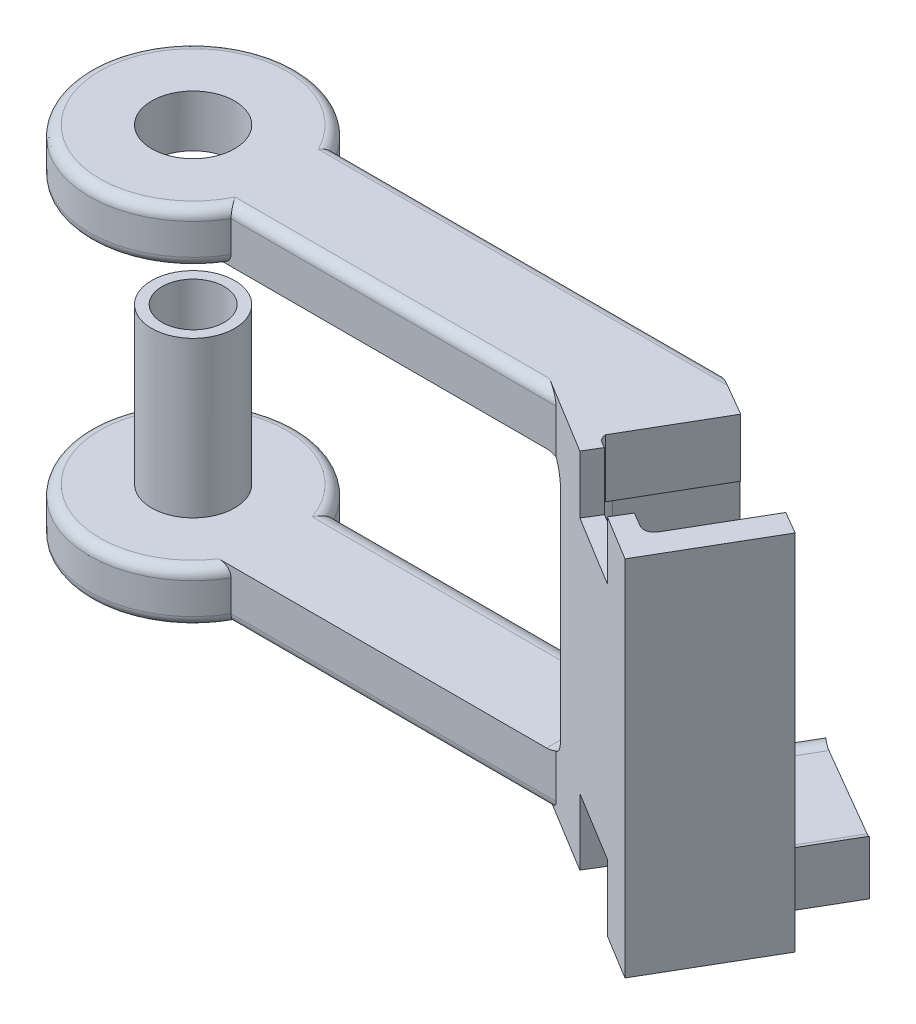
SolidWorks part; units mm, degrees
ref_plane "Front Plane" through (0, 0, 0) normal (0, 0, 1) x (1, 0, 0)
ref_plane "Top Plane" through (0, 0, 0) normal (0, 1, 0) x (1, 0, 0)
ref_plane "Right Plane" through (0, 0, 0) normal (1, 0, 0) x (0, 0, -1)
sketch "Sketch2" plane through (0, 0, 0) normal (0, 1, 0) x (1, 0, 0)
  line L0 (-20, 0) -> (20, 0) construction
  line L1 (-20, 5) -> (20, 5)
  line L2 (-20, -5) -> (20, -5)
  line L8 (25.8152, 5) -> (43.1044, -5.054)
  line L9 (20, -5) -> (37.068, -15.4252)
  line L10 (43.1044, -5.054) -> (37.068, -15.4252)
  line L11 (20, 5) -> (25.8152, 5)
  arc A0 (-20, 5) -> (-20, -5) centre (-20, 0) ccw
  circle A2 centre (-20, 0) radius 3
  point P2 (0, 0)
  dimension "D1" = 40
  dimension "D3" = 6
  dimension "D2" = 10
  dimension "D4" = 20
  dimension "D5" = 12
extrude "Boss-Extrude2" add sketch "Sketch2" along normal blind 35
sketch "Sketch3" plane through (0, 0, -5) normal (0, 0, -1) x (-1, 0, 0)
  line L6 (27.167, 30) -> (-21.0838, 30)
  line L7 (27.167, 30) -> (27.167, 5)
  line L8 (27.167, 5) -> (-21.0838, 5)
  line L9 (-21.0838, 30) -> (-21.0838, 5)
  dimension "D1" = 5
  dimension "D2" = 5
extrude "Cut-Extrude2" cut sketch "Sketch3" against normal blind 30
sketch "Sketch6" plane through (8.6965, 0, -14.9548) normal (0.5027, 0, -0.8645) x (-0.8645, 0, -0.5027)
sketch "Sketch8" plane through (8.6965, 0, -14.9548) normal (0.5027, 0, -0.8645) x (-0.8645, 0, -0.5027)
  line L0 (-39.8027, 35) -> (-19.8027, 35) construction
  point P0 (-29.8027, 35)
sketch "Sketch11" plane through (8.6965, 0, -14.9548) normal (0.5027, 0, -0.8645) x (-0.8645, 0, -0.5027)
  line L0 (-39.8027, 0) -> (-19.8027, 0) construction
  line L1 (-25.1387, 29.4) -> (-36.9387, 29.4)
  line L2 (-25.1387, 29.4) -> (-25.1387, 6.4)
  line L3 (-25.1387, 6.4) -> (-36.9387, 6.4)
  line L4 (-36.9387, 29.4) -> (-36.9387, 6.4)
  line L5 (-25.1387, 29.4) -> (-36.9387, 6.4) construction
  line L6 (-25.1387, 6.4) -> (-36.9387, 29.4) construction
  point P0 (-31.0387, 17.9)
  point P5 (-31.0387, 6.4)
  point P6 (-31.0387, 29.4)
  dimension "D1" = 11.8
  dimension "D2" = 23
  dimension "D3" = 6.4
extrude "Cut-Extrude4" cut sketch "Sketch11" against normal blind 10
sketch "Sketch13" plane through (0, 5, 0) normal (0, 1, 0) x (1, 0, 0)
  circle A0 centre (-20, 0) radius 3 construction
  circle A3 centre (-20, 0) radius 4
  circle A4 centre (-20, 0) radius 4
  point P0 (-23, 0)
  point P1 (-17, 0)
  dimension "D1" = 1
extrude "Boss-Extrude3" add sketch "Sketch13" along normal blind 15
ref_plane "Plane1" through (0, 17.5, 0) normal (0, 1, 0) x (-1, 0, 0)
sketch "Sketch15" plane through (8.6965, 0, -14.9548) normal (0.5027, 0, -0.8645) x (-0.8645, 0, -0.5027)
  line L1 (-36.9387, 29.4) -> (-25.2887, 29.4)
  line L2 (-36.9387, 29.4) -> (-36.9387, 34.4)
  line L3 (-36.9387, 34.4) -> (-25.2887, 34.4)
  line L4 (-25.2887, 29.4) -> (-25.2887, 34.4)
  line L5 (-36.9387, 6.4) -> (-25.2887, 6.4)
  line L6 (-36.9387, 6.4) -> (-36.9387, 1.4)
  line L7 (-36.9387, 1.4) -> (-25.2887, 1.4)
  line L8 (-25.2887, 6.4) -> (-25.2887, 1.4)
  dimension "D1" = 5
  dimension "D2" = 5
extrude "Boss-Extrude4" add sketch "Sketch15" along normal blind 6
sketch "Sketch19" plane through (0, 35, 0) normal (0, 1, 0) x (1, 0, 0)
  line L0 (25.8823, -8.5929) -> (31.0949, -0.0589)
  line L1 (20, -5) -> (37.068, -15.4252) construction
  line L2 (31.0949, -0.0589) -> (37.9221, -4.229)
  line L3 (37.9221, -4.229) -> (32.7095, -12.763)
  line L4 (32.7095, -12.763) -> (25.8823, -8.5929)
  line L5 (37.068, -15.4252) -> (43.1044, -5.054) construction
  point P4 (35.3158, -8.496)
  dimension "D1" = 8
  dimension "D2" = 10
  dimension "D3" = 5
extrude "Cut-Extrude7" cut sketch "Sketch19" against normal up to surface (5.6 mm away) up to face at (34.2622, 29.4, 1.2341)
sketch "Sketch20" plane through (0, 0, 0) normal (0, -1, 0) x (1, 0, 0)
  line L0 (32.7095, 12.763) -> (37.9221, 4.229)
  line L1 (20, 5) -> (37.068, 15.4252) construction
  line L2 (37.9221, 4.229) -> (31.0949, 0.0589)
  line L3 (31.0949, 0.0589) -> (25.8823, 8.5929)
  line L4 (25.8823, 8.5929) -> (32.7095, 12.763)
  line L8 (37.068, 15.4252) -> (43.1044, 5.054) construction
  point P4 (35.3158, 8.496)
  dimension "D1" = 8
  dimension "D2" = 10
  dimension "D3" = 5
extrude "Cut-Extrude8" cut sketch "Sketch20" against normal up to surface (6.4 mm away) up to face at (34.2622, 6.4, 1.2341)
ref_plane "Plane3" through (0, 0, 0) normal (0, 0, 1) x (1, 0, 0)
sketch "Sketch25" plane through (11.7127, 0, -20.1416) normal (0.5027, 0, -0.8645) x (-0.8645, 0, -0.5027)
  line L0 (-34.7329, 6.4) -> (-26.731, 6.4) construction
  line L1 (-37.3027, 35.08) -> (-25.2887, 35.08)
  line L2 (-37.3027, 35.08) -> (-37.3027, 6.4)
  line L3 (-37.3027, 6.4) -> (-25.2887, 6.4)
  line L4 (-25.2887, 35.08) -> (-25.2887, 6.4)
  line L5 (-39.8027, 35) -> (-39.8027, 0) construction
  dimension "D1" = 2.5
extrude "Cut-Extrude18" cut sketch "Sketch25" against normal blind 16
sketch "Sketch26" plane through (0, 35, 0) normal (0, 1, 0) x (1, 0, 0)
  circle A2 centre (-20, 0) radius 10
  circle A3 centre (-20, 0) radius 10
  dimension "D1" = 7
extrude "Boss-Extrude7" add sketch "Sketch26" against normal blind 5
sketch "Sketch27" plane through (0, 0, 0) normal (0, -1, 0) x (1, 0, 0)
  circle A2 centre (-20, 0) radius 10
  circle A3 centre (-20, 0) radius 10
  dimension "D1" = 7
extrude "Boss-Extrude8" add sketch "Sketch27" against normal blind 5
sketch "Sketch28" plane through (0, 0, 0) normal (0, 0, 1) x (1, 0, 0)
sketch "Sketch29" plane through (0, 35, 0) normal (0, 1, 0) x (1, 0, 0)
  arc A2 (-17.4019, 1.5) -> (-17.4019, -1.5) centre (-20, 0) ccw
  circle A3 centre (-20, 0) radius 3
  dimension "D1" = 7
extrude "Cut-Extrude19" cut sketch "Sketch29" against normal through all both and the other way through all
sketch "Sketch30" plane through (0, 35, 0) normal (0, 1, 0) x (1, 0, 0)
  circle A2 centre (-20, 0) radius 4
  circle A3 centre (-20, 0) radius 4
  dimension "D1" = 1
extrude "Cut-Extrude20" cut sketch "Sketch30" against normal up to next
fillet "Fillet8" radius 1 3 edges at (-30, 35, 0) (4.3301, 35, 5) (7.2377, 35, -5)
fillet "Fillet9" radius 2 1 edges at (21.0838, 5, 0.331)
fillet "Fillet10" radius 2 1 edges at (21.0838, 30, 0.331)
fillet "Fillet11" radius 2 5 edges at (3.872, 5, -5) (3.872, 30, -5) (20.498, 29.4142, -5) (21.0838, 17.5, -5) (20.498, 5.5858, -5)
fillet "Fillet12" radius 1 5 edges at (-29.9402, 30, -1.0923) (-29.9402, 5, -1.0923) (-30, 0, 0) (7.2377, 0, -5) (4.3301, 0, 5)
fillet "Fillet15" radius 1 2 edges at (38.4298, 6.4, 8.1195) (27.9144, 6.4, 2.0047)
fillet "Fillet16" radius 1 6 edges at (26.5214, 6.4, 6.9786) (25.6541, 6.6929, 6.4743) (34.3732, 6.4, 11.5446) (35.6631, 6.6929, 12.2946) (25.4009, 18.4, 6.327) (35.9163, 21.2, 12.4418)
